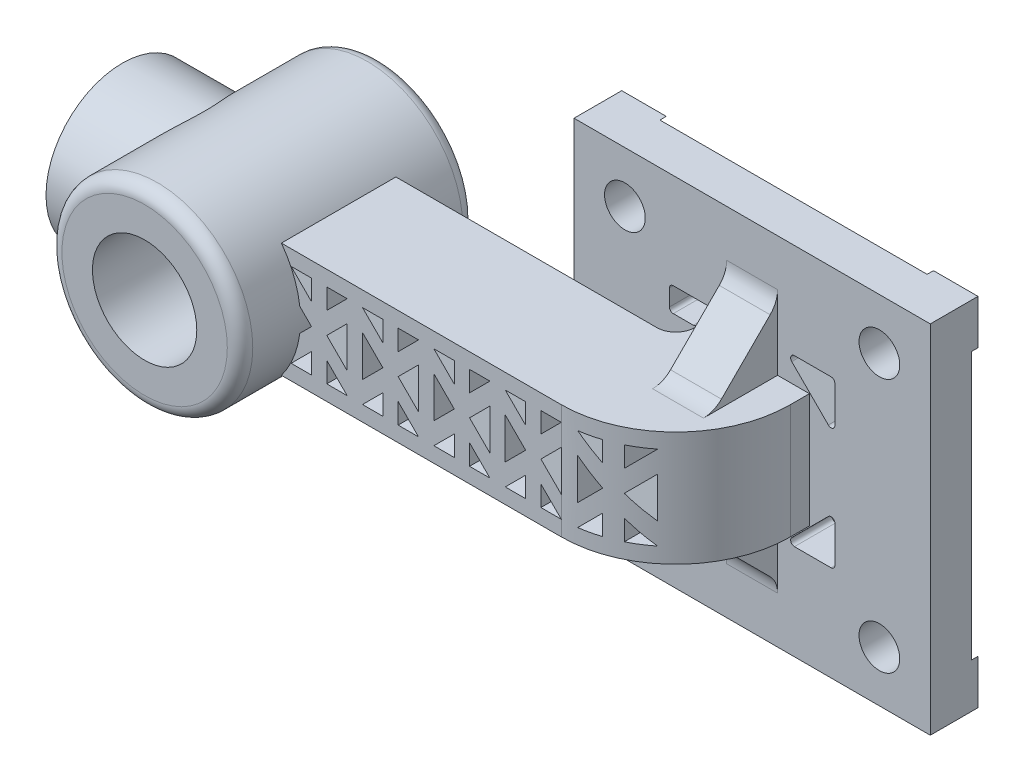
SolidWorks part; units mm, degrees
ref_plane "Front Plane" through (0, 0, 0) normal (0, 0, 1) x (1, 0, 0)
ref_plane "Top Plane" through (0, 0, 0) normal (0, 1, 0) x (1, 0, 0)
ref_plane "Right Plane" through (0, 0, 0) normal (1, 0, 0) x (0, 0, -1)
sketch "Sketch1" plane through (0, 0, 0) normal (0, 0, 1) x (1, 0, 0)
  line L1 (0, 0) -> (28, 0)
  line L2 (0, 0) -> (0, 28)
  line L3 (0, 28) -> (28, 28)
  line L4 (28, 0) -> (28, 28)
  dimension "D1" = 28
  dimension "D2" = 28
extrude "Boss-Extrude1" add sketch "Sketch1" along normal blind 3.25
sketch "Sketch3" plane through (0, 0, 0) normal (0, 0, -1) x (-1, 0, 0)
  line L0 (-14, 28) -> (-14, 0) construction
  line L1 (-28, 28) -> (0, 28) construction
  line L2 (0, 0) -> (-28, 0) construction
  circle A0 centre (-24, 24) radius 1.6
  circle A1 centre (-4, 24) radius 1.6
  circle A2 centre (-4, 4) radius 1.6
  circle A3 centre (-24, 4) radius 1.6
  point P8 (-14, 14)
  dimension "D5" = 3.2
  dimension "D6" = 3.2
  dimension "D7" = 3.2
  dimension "D8" = 3.2
  dimension "D1" = 20
  dimension "D2" = 20
  dimension "D3" = 10
  dimension "D4" = 10
extrude "Cut-Extrude1" cut sketch "Sketch3" against normal through all
sketch "Sketch4" plane through (0, 0, 0) normal (0, 0, -1) x (-1, 0, 0)
  line L0 (-14, 28) -> (-14, 0) construction
  line L1 (-20.5, 25.5) -> (-7.5, 25.5)
  line L2 (-20.5, 25.5) -> (-20.5, 23)
  line L3 (-20.5, 23) -> (-7.5, 23)
  line L4 (-7.5, 25.5) -> (-7.5, 23)
  line L5 (-28, 28) -> (0, 28) construction
  line L6 (0, 0) -> (-28, 0) construction
  line L7 (0, 14) -> (-28, 14) construction
  line L8 (0, 28) -> (0, 0) construction
  line L9 (-28, 0) -> (-28, 28) construction
  line L11 (-5, 20.5) -> (-2.5, 20.5)
  line L12 (-5, 20.5) -> (-5, 7.5)
  line L13 (-5, 7.5) -> (-2.5, 7.5)
  line L14 (-2.5, 20.5) -> (-2.5, 7.5)
  line L15 (-7.5, 5) -> (-20.5, 5)
  line L16 (-7.5, 5) -> (-7.5, 2.5)
  line L17 (-7.5, 2.5) -> (-20.5, 2.5)
  line L18 (-20.5, 5) -> (-20.5, 2.5)
  line L19 (-23, 7.5) -> (-25.5, 7.5)
  line L20 (-23, 7.5) -> (-23, 20.5)
  line L21 (-23, 20.5) -> (-25.5, 20.5)
  line L22 (-25.5, 7.5) -> (-25.5, 20.5)
  dimension "D1" = 13
  dimension "D2" = 6.5
  dimension "D3" = 2.5
  dimension "D4" = 2.5
  dimension "D5" = 2.5
  dimension "D6" = 2.5
  dimension "D7" = 13
  dimension "D8" = 6.5
  dimension "D9" = 2.5
  dimension "D10" = 2.5
  dimension "D11" = 13
  dimension "D12" = 6.5
  dimension "D13" = 2.5
  dimension "D14" = 2.5
  dimension "D15" = 13
  dimension "D16" = 6.5
extrude "Boss-Extrude3" add sketch "Sketch4" along normal blind 0.5
sketch "Sketch5" plane through (0, 0, 3.25) normal (0, 0, 1) x (1, 0, 0)
  line L0 (28, 28) -> (0, 28) construction
  line L1 (9.5, 9.5) -> (18.5, 9.5)
  line L2 (9.5, 9.5) -> (9.5, 18.5)
  line L3 (9.5, 18.5) -> (18.5, 18.5)
  line L4 (18.5, 9.5) -> (18.5, 18.5)
  line L5 (28, 0) -> (28, 28) construction
  dimension "D1" = 9
  dimension "D2" = 9
  dimension "D3" = 9.5
  dimension "D4" = 9.5
extrude "Boss-Extrude4" add sketch "Sketch5" along normal blind 10.5
sketch "Sketch6" plane through (9.5, 0, 0) normal (-1, 0, 0) x (0, 0, 1)
  line L0 (13.75, 9.5) -> (3.25, 9.5) construction
  line L1 (13.75, 18.5) -> (4.75, 18.5)
  line L2 (13.75, 18.5) -> (13.75, 9.5)
  line L3 (13.75, 9.5) -> (4.75, 9.5)
  line L4 (4.75, 18.5) -> (4.75, 9.5)
  dimension "D1" = 9
extrude "Boss-Extrude5" add sketch "Sketch6" along normal blind 28
fillet "Fillet1" radius 9 1 edges at (18.5, 14, 13.75)
fillet "Fillet2" radius 1.5 1 edges at (9.5, 14, 4.75)
sketch "Sketch7" plane through (0, 0, 0) normal (0, 0, 1) x (1, 0, 0)
  line L0 (9.5, 14) -> (-26.4195, 14) construction
  line L1 (9.5, 9.5) -> (9.5, 18.5) construction
  line L2 (-18.5, 9.5) -> (-18.5, 18.5) construction
  circle A1 centre (-18.5, 14) radius 7.5
  dimension "D2" = 15
sketch "Sketch8" plane through (-18.5, 0, 0) normal (-1, 0, 0) x (0, 0, 1)
  line L0 (9.25, 18.5) -> (9.25, 9.5) construction
  line L1 (13.75, 18.5) -> (4.75, 18.5) construction
  line L2 (4.75, 9.5) -> (13.75, 9.5) construction
  circle A0 centre (9.25, 14) radius 6
  dimension "D1" = 12
extrude "Boss-Extrude7" add sketch "Sketch8" along normal blind 11
sketch "Sketch18" plane through (0, 0, 13.75) normal (0, 0, 1) x (1, 0, 0)
  line L0 (9.5, 12.3971) -> (9.5, 15.6029)
  line L1 (9.5, 14) -> (-15.7073, 14) construction
  line L2 (9.5, 9.5) -> (9.5, 18.5) construction
  line L3 (9.5, 15.6029) -> (7.8971, 14)
  line L4 (7.8971, 14) -> (9.5, 12.3971)
  line L5 (7.8971, 15.6971) -> (9.5, 17.3)
  line L6 (9.5, 17.3) -> (7.8971, 17.3)
  line L7 (7.8971, 17.3) -> (7.8971, 15.6971)
  line L8 (9.5, 10.7) -> (7.8971, 10.7)
  line L9 (9.5, 18.5) -> (-18.5, 18.5) construction
  line L10 (7.8971, 10.7) -> (7.8971, 12.3029)
  line L11 (7.8971, 12.3029) -> (9.5, 10.7)
  line L12 (-18.5, 9.5) -> (9.5, 9.5) construction
  line L13 (6.6971, 17.3) -> (6.6971, 15.6971)
  line L14 (6.6971, 15.6971) -> (5.0941, 17.3)
  line L15 (5.0941, 17.3) -> (6.6971, 17.3)
  line L16 (6.6971, 14) -> (5.0941, 15.6029)
  line L17 (5.0941, 15.6029) -> (5.0941, 12.3971)
  line L18 (5.0941, 12.3971) -> (6.6971, 14)
  line L19 (5.0941, 10.7) -> (6.6971, 10.7)
  line L20 (6.6971, 10.7) -> (6.6971, 12.3029)
  line L21 (6.6971, 12.3029) -> (5.0941, 10.7)
  line L22 (3.89, 12.3971) -> (3.89, 15.6029)
  line L23 (3.89, 15.6029) -> (2.2871, 14)
  line L24 (2.2871, 14) -> (3.89, 12.3971)
  line L25 (2.2871, 15.6971) -> (3.89, 17.3)
  line L26 (3.89, 17.3) -> (2.2871, 17.3)
  line L27 (2.2871, 17.3) -> (2.2871, 15.6971)
  line L28 (3.89, 10.7) -> (2.2871, 10.7)
  line L29 (2.2871, 10.7) -> (2.2871, 12.3029)
  line L30 (2.2871, 12.3029) -> (3.89, 10.7)
  line L31 (1.0871, 17.3) -> (1.0871, 15.6971)
  line L32 (1.0871, 15.6971) -> (-0.5159, 17.3)
  line L33 (-0.5159, 17.3) -> (1.0871, 17.3)
  line L34 (1.0871, 14) -> (-0.5159, 15.6029)
  line L35 (-0.5159, 15.6029) -> (-0.5159, 12.3971)
  line L36 (-0.5159, 12.3971) -> (1.0871, 14)
  line L37 (-0.5159, 10.7) -> (1.0871, 10.7)
  line L38 (1.0871, 10.7) -> (1.0871, 12.3029)
  line L39 (1.0871, 12.3029) -> (-0.5159, 10.7)
  line L40 (-1.72, 12.3971) -> (-1.72, 15.6029)
  line L41 (-1.72, 15.6029) -> (-3.3229, 14)
  line L42 (-3.3229, 14) -> (-1.72, 12.3971)
  line L43 (-3.3229, 15.6971) -> (-1.72, 17.3)
  line L44 (-1.72, 17.3) -> (-3.3229, 17.3)
  line L45 (-3.3229, 17.3) -> (-3.3229, 15.6971)
  line L46 (-1.72, 10.7) -> (-3.3229, 10.7)
  line L47 (-3.3229, 10.7) -> (-3.3229, 12.3029)
  line L48 (-3.3229, 12.3029) -> (-1.72, 10.7)
  line L49 (-4.5229, 17.3) -> (-4.5229, 15.6971)
  line L50 (-4.5229, 15.6971) -> (-6.1259, 17.3)
  line L51 (-6.1259, 17.3) -> (-4.5229, 17.3)
  line L52 (-4.5229, 14) -> (-6.1259, 15.6029)
  line L53 (-6.1259, 15.6029) -> (-6.1259, 12.3971)
  line L54 (-6.1259, 12.3971) -> (-4.5229, 14)
  line L55 (-6.1259, 10.7) -> (-4.5229, 10.7)
  line L56 (-4.5229, 10.7) -> (-4.5229, 12.3029)
  line L57 (-4.5229, 12.3029) -> (-6.1259, 10.7)
  line L58 (-7.33, 12.3971) -> (-7.33, 15.6029)
  line L59 (-7.33, 15.6029) -> (-8.9329, 14)
  line L60 (-8.9329, 14) -> (-7.33, 12.3971)
  line L61 (-8.9329, 15.6971) -> (-7.33, 17.3)
  line L62 (-7.33, 17.3) -> (-8.9329, 17.3)
  line L63 (-8.9329, 17.3) -> (-8.9329, 15.6971)
  line L64 (-7.33, 10.7) -> (-8.9329, 10.7)
  line L65 (-8.9329, 10.7) -> (-8.9329, 12.3029)
  line L66 (-8.9329, 12.3029) -> (-7.33, 10.7)
  line L67 (-10.1329, 17.3) -> (-10.1329, 15.6971)
  line L68 (-10.1329, 15.6971) -> (-11.7359, 17.3)
  line L69 (-11.7359, 17.3) -> (-10.1329, 17.3)
  line L70 (-10.1329, 14) -> (-11.7359, 15.6029)
  line L71 (-11.7359, 15.6029) -> (-11.7359, 12.3971)
  line L72 (-11.7359, 12.3971) -> (-10.1329, 14)
  line L73 (-11.7359, 10.7) -> (-10.1329, 10.7)
  line L74 (-10.1329, 10.7) -> (-10.1329, 12.3029)
  line L75 (-10.1329, 12.3029) -> (-11.7359, 10.7)
  line L76 (15.11, 12.3971) -> (15.11, 15.6029)
  line L77 (15.11, 15.6029) -> (13.5071, 14)
  line L78 (13.5071, 14) -> (15.11, 12.3971)
  line L79 (13.5071, 15.6971) -> (15.11, 17.3)
  line L80 (15.11, 17.3) -> (13.5071, 17.3)
  line L81 (13.5071, 17.3) -> (13.5071, 15.6971)
  line L82 (15.11, 10.7) -> (13.5071, 10.7)
  line L83 (13.5071, 10.7) -> (13.5071, 12.3029)
  line L84 (13.5071, 12.3029) -> (15.11, 10.7)
  line L85 (12.3071, 17.3) -> (12.3071, 15.6971)
  line L86 (12.3071, 15.6971) -> (10.7041, 17.3)
  line L87 (10.7041, 17.3) -> (12.3071, 17.3)
  line L88 (12.3071, 14) -> (10.7041, 15.6029)
  line L89 (10.7041, 15.6029) -> (10.7041, 12.3971)
  line L90 (10.7041, 12.3971) -> (12.3071, 14)
  line L91 (10.7041, 10.7) -> (12.3071, 10.7)
  line L92 (12.3071, 10.7) -> (12.3071, 12.3029)
  line L93 (12.3071, 12.3029) -> (10.7041, 10.7)
  line L94 (15.11, 14) -> (-10.0973, 14) construction
  dimension "D1" = 45
  dimension "D2" = 45
  dimension "D3" = 1.2
  dimension "D4" = 1.2
  dimension "D5" = 1.2
  dimension "D6" = 1.2
  dimension "D7" = 1.2
  dimension "D8" = 45
  dimension "D9" = 1.2
  dimension "D10" = 1.2
  dimension "D11" = 0
  dimension "D12" = 4
  dimension "D13" = 2
extrude "Cut-Extrude4" cut sketch "Sketch18" against normal blind 9
extrude "Boss-Extrude8" add sketch "Sketch7" along normal blind 18.5
sketch "Sketch9" plane through (0, 0, 18.5) normal (0, 0, 1) x (1, 0, 0)
  line L0 (-18.5, 21.5) -> (-18.5, 6.5) construction
  circle A0 centre (-18.5, 14) radius 7.5 construction
  circle A1 centre (-18.5, 14) radius 4.1
  dimension "D1" = 8.2
extrude "Cut-Extrude2" cut sketch "Sketch9" against normal through all
sketch "Sketch11" plane through (-29.5, 0, 0) normal (-1, 0, 0) x (0, 0, 1)
  line L0 (9.25, 20) -> (9.25, 8) construction
  circle A0 centre (9.25, 14) radius 6 construction
  circle A1 centre (9.25, 14) radius 6 construction
  circle A2 centre (9.25, 14) radius 2.5
  dimension "D1" = 5
extrude "Cut-Extrude3" cut sketch "Sketch11" against normal blind 9
sketch "Sketch14" plane through (0, 0, 0) normal (1, 0, 0) x (0, 0, -1)
  line L0 (-8.25, 18.5) -> (-3.25, 23.5)
  line L1 (-4.75, 18.5) -> (-13.75, 18.5) construction
  line L2 (-3.25, 0) -> (-3.25, 28) construction
  line L3 (-3.25, 23.5) -> (-3.25, 18.5)
  line L4 (-3.25, 18.5) -> (-8.25, 18.5)
  line L5 (-8.25, 9.5) -> (-3.25, 4.5)
  line L6 (-4.75, 9.5) -> (-13.75, 9.5) construction
  line L7 (-3.25, 4.5) -> (-3.25, 9.5)
  line L8 (-3.25, 9.5) -> (-8.25, 9.5)
  dimension "D1" = 5
  dimension "D2" = 5
  dimension "D3" = 5
  dimension "D4" = 5
extrude "Boss-Extrude10" add sketch "Sketch14" along normal blind 4 from offset 12
fillet "Fillet3" radius 2 4 edges at (14, 4.5, 3.25) (14, 9.5, 8.25) (14, 18.5, 8.25) (14, 23.5, 3.25)
sketch "Sketch15" plane through (0, 9.5, 0) normal (0, -1, 0) x (1, 0, 0)
  line L0 (-12.5, 4.75) -> (8, 4.75) construction
  line L1 (1.8172, 4.75) -> (10.75, 4.75)
  line L2 (1.8172, 4.75) -> (1.8172, 3.25)
  line L3 (1.8172, 3.25) -> (10.75, 3.25)
  line L4 (10.75, 4.75) -> (10.75, 3.25)
  line L5 (9.5, 3.25) -> (12, 3.25) construction
extrude "Boss-Extrude11" add sketch "Sketch15" against normal blind 3 from offset 3 offset against normal yes
fillet "Fillet4" radius 1 1 edges at (-11, 14, 0)
fillet "Fillet5" radius 1 1 edges at (-11, 14, 18.5)
sketch "Sketch19" plane through (0, 0, 0) normal (0, 0, -1) x (-1, 0, 0)
  line L0 (-20.5, 20.5) -> (-20.5, 16.6)
  line L1 (-20.5, 16.6) -> (-16.6, 20.5)
  line L2 (-16.6, 20.5) -> (-20.5, 20.5)
  line L3 (-11.4, 20.5) -> (-7.6, 16.7) construction
  line L4 (-20.5, 25.5) -> (-20.5, 23) construction
  line L5 (-23, 20.5) -> (-25.5, 20.5) construction
  line L6 (-20.5, 7.5) -> (-20.5, 11.4)
  line L7 (-20.5, 11.4) -> (-16.6, 7.5)
  line L8 (-16.6, 7.5) -> (-20.5, 7.5)
  line L9 (-7.5, 7.5) -> (-11.4, 7.5)
  line L11 (-7.5, 9.4) -> (-7.5, 7.5)
  line L13 (-11.4, 20.5) -> (-7.5, 20.5)
  line L14 (-7.5, 20.5) -> (-7.5, 18.6)
  line L15 (-25.5, 7.5) -> (-23, 7.5) construction
  line L16 (-7.5, 23) -> (-7.5, 25.5) construction
  line L17 (-7.5, 18.6) -> (-9.5, 18.6)
  line L18 (-9.5, 18.6) -> (-11.4, 20.5)
  line L19 (-11.4, 7.5) -> (-7.111, 11.789) construction
  line L20 (-7.5, 9.4) -> (-9.5, 9.4)
  line L21 (-9.5, 9.4) -> (-11.4, 7.5)
  point P17 (0, 0)
  dimension "D1" = 0
  dimension "D2" = 0
  dimension "D3" = 3.9
  dimension "D4" = 3.9
  dimension "D5" = 0
  dimension "D6" = 0
  dimension "D7" = 3.9
  dimension "D8" = 1.9
  dimension "D9" = 1.9
  dimension "D10" = 3.9
  dimension "D11" = 3.9
  dimension "D12" = 3.9
  dimension "D13" = 45
  dimension "D14" = 45
extrude "Cut-Extrude5" cut sketch "Sketch19" against normal blind 10
fillet "Fillet6" radius 0.3 14 edges at (9.5, 9.4, 1.625) (7.5, 18.6, 1.625) (7.5, 20.5, 1.625) (11.4, 20.5, 1.625) (9.5, 18.6, 1.625) (11.4, 7.5, 1.625) (7.5, 9.4, 1.625) (7.5, 7.5, 1.625) (16.6, 7.5, 1.625) (20.5, 7.5, 1.625) (20.5, 11.4, 1.625) (16.6, 20.5, 1.625) (20.5, 20.5, 1.625) (20.5, 16.6, 1.625)
sketch "Sketch20" plane through (0, 0, 0) normal (0, 0, -1) x (-1, 0, 0)
  line L0 (-14, 28) -> (-14, 0) construction
  line L1 (-28, 28) -> (0, 28) construction
  line L2 (0, 0) -> (-28, 0) construction
  circle A0 centre (-14, 14) radius 3.5
  dimension "D1" = 7
extrude "Cut-Extrude6" cut sketch "Sketch20" against normal blind 0.5
sketch "Sketch21" plane through (0, 0, 0) normal (0, 0, -1) x (-1, 0, 0)
  line L0 (-28, 28) -> (-28, 24.5)
  line L1 (-28, 0) -> (-28, 28) construction
  line L2 (-28, 24.5) -> (-24.5, 28)
  line L3 (-28, 28) -> (0, 28) construction
  line L4 (-24.5, 28) -> (-28, 28)
  line L5 (-3.5, 28) -> (0, 24.5)
  line L6 (0, 28) -> (0, 0) construction
  line L7 (0, 24.5) -> (0, 28)
  line L8 (0, 28) -> (-3.5, 28)
  line L9 (-3.5, 0) -> (0, 0)
  line L10 (0, 0) -> (-28, 0) construction
  line L11 (0, 0) -> (0, 3.5)
  line L12 (0, 3.5) -> (-3.5, 0)
  line L13 (-28, 0) -> (-28, 3.5)
  line L14 (-28, 3.5) -> (-24.5, 0)
  line L15 (-24.5, 0) -> (-28, 0)
  dimension "D1" = 3.5
  dimension "D2" = 3.5
  dimension "D3" = 3.5
  dimension "D4" = 3.5
  dimension "D5" = 3.5
  dimension "D6" = 3.5
  dimension "D7" = 3.5
  dimension "D8" = 3.5
extrude "Boss-Extrude12" add sketch "Sketch21" along normal blind 0.5
